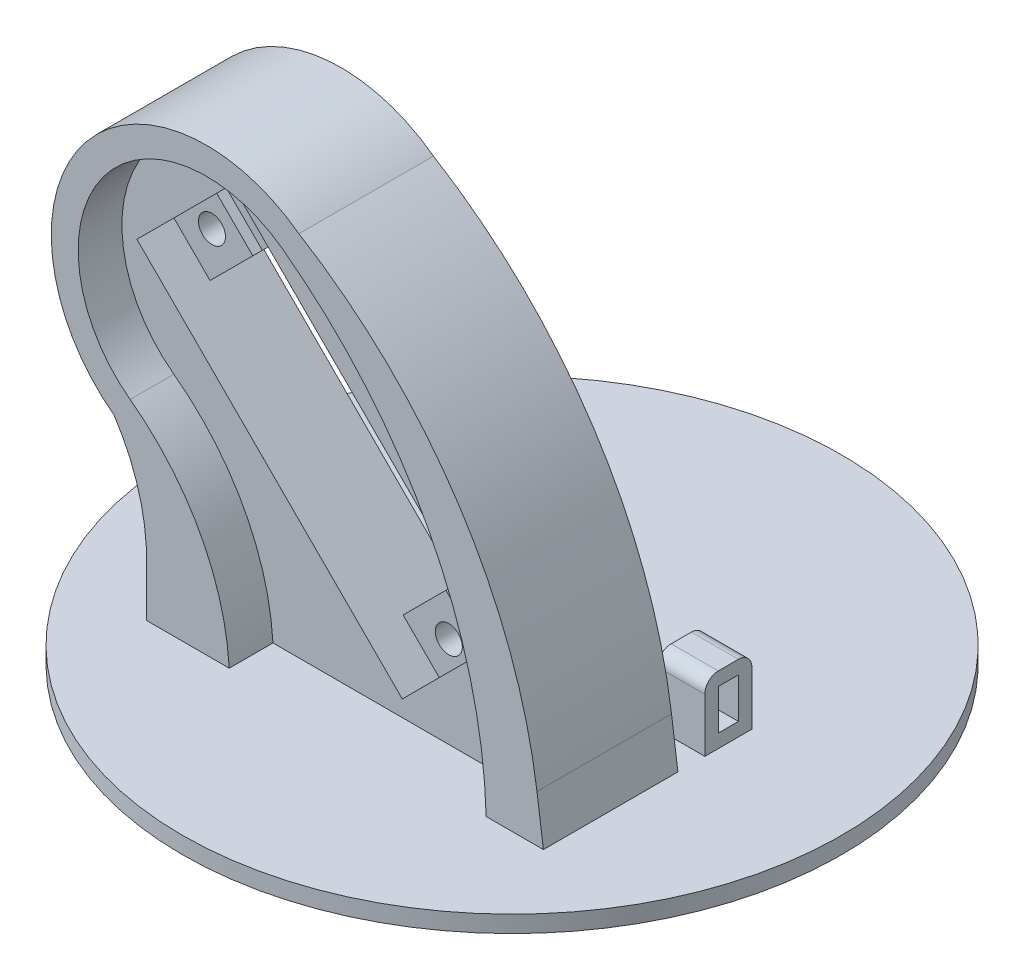
SolidWorks part; units mm, degrees
ref_plane "Front Plane" through (0, 0, 0) normal (0, 0, 1) x (1, 0, 0)
ref_plane "Top Plane" through (0, 0, 0) normal (0, 1, 0) x (1, 0, 0)
ref_plane "Right Plane" through (0, 0, 0) normal (1, 0, 0) x (0, 0, -1)
sketch "Sketch1" plane through (0, 0, 0) normal (0, 1, 0) x (1, 0, 0)
  circle A0 centre (0, 0) radius 49
  dimension "D1" = 98
extrude "Boss-Extrude1" add sketch "Sketch1" along normal blind 4
ref_plane "Plane1" through (0, 0, 4) normal (0, 0, 1) x (1, 0, 0)
sketch "Sketch3" plane through (0, 0, 4) normal (0, 0, 1) x (1, 0, 0)
  line L0 (-30.3479, 4) -> (28.6566, 4)
  line L2 (0, 11) -> (-28.4964, 39.4964)
  line L3 (14.1421, 25.1421) -> (-14.3543, 53.6385)
  line L4 (0, 11) -> (14.1421, 25.1421)
  line L5 (-28.4964, 39.4964) -> (-14.3543, 53.6385)
  line L6 (-30.3479, 4) -> (-30.3479, 11)
  line L9 (-14.2977, 39.4398) -> (-7.2266, 46.5109) construction
  line L10 (27.7023, 11) -> (28.6566, 4)
  circle A0 centre (-14.2977, 39.4398) radius 6
  arc A1 (-21.4253, 46.5675) -> (1.0561, 4) centre (-54.544, 1.8559) cw construction
  arc A2 (20.1509, 4) -> (-10.0661, 61.9029) centre (-54.544, 1.8559) ccw
  arc A3 (-18.0498, 4) -> (-32.7846, 31.232) centre (-54.544, 1.8559) ccw
  arc A5 (-10.0661, 61.9029) -> (-32.7846, 31.232) centre (-21.4253, 46.5675) ccw
  arc A7 (-7.6852, 65.1172) -> (-35.1655, 28.0178) centre (-21.4253, 46.5675) ccw
  arc A12 (5.5029, -42.622) -> (-10.0661, 61.9029) centre (-54.544, 1.8559) ccw construction
  arc A13 (-25.1679, -19.9035) -> (-32.7846, 31.232) centre (-54.544, 1.8559) ccw construction
  arc A14 (-28.3822, -17.5227) -> (8.7172, -45.0029) centre (-9.8325, -31.2628) ccw construction
  arc A15 (-28.3822, -17.5227) -> (-35.1655, 28.0178) centre (-54.544, 1.8559) ccw construction
  arc A16 (-25.1679, -19.9035) -> (5.5029, -42.622) centre (-9.8325, -31.2628) ccw construction
  arc A17 (8.7172, -45.0029) -> (-7.6852, 65.1172) centre (-54.544, 1.8559) ccw construction
  arc A18 (-30.3479, 11) -> (-35.1655, 28.0178) centre (-59.8626, 11.8355) ccw
  arc A19 (-7.6852, 65.1172) -> (27.7023, 11) centre (-46.9322, 0.8247) cw
  point P16 (0.4903, 10.0533)
  dimension "D6" = 12
  dimension "D1" = 4
  dimension "D3" = 40.3
  dimension "D5" = 10.08
  dimension "D4" = 20
extrude "Boss-Extrude2" add sketch "Sketch3" along normal blind 20 contours A19 A7 A18 L6 L0 A3 A5 A2 L10 region at (-29.3649, 7.5, 4)
extrude "Boss-Extrude3" add sketch "Sketch3<3>" along normal blind 13.5 contours A2 A5 A3 L0 L2 L5 L3 L4 region at (-21.631, 19.6646, 4)
sketch "Sketch3<3>" plane through (0, 0, 4) normal (0, 0, 1) x (1, 0, 0) same geometry as "Sketch3"
extrude "Boss-Extrude4" add sketch "Sketch3<4>" along normal up to surface (13.5 mm away) contours A0 | L5 L2 L4 L3 A0 region at (-6.0149, 31.157, 4) region at (-14.2977, 39.4398, 4) up to face at (-7.1771, 32.3193, 17.5)
sketch "Sketch3<4>" plane through (0, 0, 4) normal (0, 0, 1) x (1, 0, 0) same geometry as "Sketch3"
sketch "Sketch5" plane through (0, 0, 17.5) normal (0, 0, 1) x (1, 0, 0)
  line L0 (15.3215, 20.5473) -> (-24.1351, 60.0039)
  line L1 (1.1794, 6.4052) -> (-38.2772, 45.8618)
  line L2 (-38.2772, 45.8618) -> (-24.1351, 60.0039)
  line L3 (1.1794, 6.4052) -> (15.3215, 20.5473)
extrude "Cut-Extrude5" cut sketch "Sketch5" against normal blind 5.5
sketch "Sketch8" plane through (0, 0, 12) normal (0, 0, 1) x (1, 0, 0)
  line L0 (-32.9032, 40.4878) -> (-18.761, 54.6299)
  line L1 (-38.2772, 45.8618) -> (1.1794, 6.4052) construction
  line L2 (15.3215, 20.5473) -> (-24.1351, 60.0039) construction
  line L3 (-4.1946, 11.7792) -> (9.9475, 25.9214)
  line L4 (-24.1351, 60.0039) -> (-38.2772, 45.8618) construction
  line L11 (1.1794, 6.4052) -> (15.3215, 20.5473)
  line L12 (15.3215, 20.5473) -> (-24.1351, 60.0039)
  line L13 (-24.1351, 60.0039) -> (-38.2772, 45.8618)
  line L14 (-38.2772, 45.8618) -> (1.1794, 6.4052)
  line L15 (1.1794, 6.4052) -> (15.3215, 20.5473)
  line L16 (15.3215, 20.5473) -> (-24.1351, 60.0039)
  line L17 (-24.1351, 60.0039) -> (-38.2772, 45.8618)
  line L18 (-38.2772, 45.8618) -> (1.1794, 6.4052)
  line M8 (15.3215, 20.5473) -> (-24.1351, 60.0039)
  line M10 (-38.2772, 45.8618) -> (1.1794, 6.4052)
  dimension "D1" = 7.6
  dimension "D2" = 0
extrude "Cut-Extrude6" cut sketch "Sketch8" against normal blind 9 contours L3 L0 M10 M8 region at (-11.4778, 33.2046, 12)
sketch "Sketch11" plane through (0, 4, 0) normal (0, 1, 0) x (1, 0, 0)
  line L0 (28.6566, 0) -> (28.6566, 7)
  line L1 (28.6566, 7) -> (21.6566, 7)
  line L2 (21.6566, 7) -> (21.6566, 0)
  line L3 (21.6566, 0) -> (28.6566, 0)
  dimension "D1" = 7
  dimension "D2" = 7
extrude "Boss-Extrude5" add sketch "Sketch11" along normal blind 10
sketch "Sketch12" plane through (21.6566, 0, 0) normal (-1, 0, 0) x (0, 0, 1)
  line L8 (-5, 6) -> (-2, 6)
  line L9 (-2, 6) -> (-2, 12)
  line L10 (-2, 12) -> (-5, 12)
  line L11 (-5, 12) -> (-5, 6)
  line L12 (-5, 6) -> (-2, 6)
  line L13 (-2, 6) -> (-2, 12)
  line L14 (-2, 12) -> (-5, 12)
  line L15 (-5, 12) -> (-5, 6)
  dimension "D1" = 2
extrude "Cut-Extrude9" cut sketch "Sketch12" against normal up to next
fillet "Fillet1" radius 2 2 edges at (25.1566, 14, 0) (25.1566, 14, -7)
sketch "Sketch13" plane through (0, 4, 0) normal (0, 1, 0) x (1, 0, 0)
  circle A0 centre (0, 0) radius 1.27
  dimension "D1" = 2.54
extrude "Cut-Extrude10" cut sketch "Sketch13" against normal up to next
sketch "Sketch14" plane through (0, 0, 17.5) normal (0, 0, 1) x (1, 0, 0)
  line L0 (-49, 1.5) -> (50.2317, 1.5)
  line L1 (-49, 4) -> (-49, 0) construction
  line L2 (50.2317, 1.5) -> (50.2317, 0)
  line L3 (50.2317, 0) -> (-50.3039, 0)
  line L4 (-50.3039, 0) -> (-50.3039, 1.5)
  line L5 (-50.3039, 1.5) -> (-49, 1.5)
  dimension "D1" = 1.5
extrude "Cut-Extrude11" cut sketch "Sketch14" against normal mid plane 190
sketch "Sketch16" plane through (0, 0, 12) normal (0, 0, 1) x (1, 0, 0)
  line L0 (-31.2061, 52.9328) -> (8.2504, 13.4763) construction
  line L1 (-24.1351, 60.0039) -> (-38.2772, 45.8618) construction
  line L2 (1.1794, 6.4052) -> (15.3215, 20.5473) construction
  line L4 (-31.9132, 52.2257) -> (-26.5392, 46.8517)
  line L5 (-30.499, 53.6399) -> (-25.125, 48.2659)
  line L6 (8.9575, 14.1834) -> (3.5835, 19.5574)
  line L8 (-4.1946, 11.7792) -> (9.9475, 25.9214) construction
  line L9 (7.5433, 12.7692) -> (2.1693, 18.1432)
  line L10 (-38.2772, 45.8618) -> (-32.9032, 40.4878)
  line L11 (-32.9032, 40.4878) -> (-18.761, 54.6299)
  line L12 (-18.761, 54.6299) -> (-24.1351, 60.0039)
  line L13 (-24.1351, 60.0039) -> (-38.2772, 45.8618)
  line L14 (-38.2772, 45.8618) -> (-32.9032, 40.4878)
  line L15 (-32.9032, 40.4878) -> (-18.761, 54.6299)
  line L16 (-18.761, 54.6299) -> (-24.1351, 60.0039)
  line L17 (-24.1351, 60.0039) -> (-38.2772, 45.8618)
  line L22 (9.9475, 25.9214) -> (-4.1946, 11.7792)
  line L23 (-4.1946, 11.7792) -> (1.1794, 6.4052)
  line L24 (1.1794, 6.4052) -> (15.3215, 20.5473)
  line L25 (15.3215, 20.5473) -> (9.9475, 25.9214)
  line L26 (9.9475, 25.9214) -> (-4.1946, 11.7792)
  line L27 (-4.1946, 11.7792) -> (1.1794, 6.4052)
  line L28 (1.1794, 6.4052) -> (15.3215, 20.5473)
  line L29 (15.3215, 20.5473) -> (9.9475, 25.9214)
  line M12 (9.9475, 25.9214) -> (-4.1946, 11.7792)
  line M14 (1.1794, 6.4052) -> (15.3215, 20.5473)
  dimension "D1" = 0
  dimension "D2" = 2
  dimension "D3" = 1
  dimension "D4" = 0
extrude "Cut-Extrude12" cut sketch "Sketch16" against normal blind 2 contours L0 L28 L6 M12 | L0 L26 L9 M14 region at (5.917, 16.5168, 12) region at (5.2099, 15.8097, 12)
extrude "Cut-Extrude13" cut sketch "Sketch16<3>" against normal blind 2 contours L0 L17 L4 L15 | L17 L0 L15 L5 region at (-28.1656, 50.5994, 12) region at (-28.8727, 49.8923, 12)
sketch "Sketch16<3>" plane through (0, 0, 12) normal (0, 0, 1) x (1, 0, 0) same geometry as "Sketch16"
sketch "Sketch17" plane through (0, 4, 0) normal (0, 1, 0) x (1, 0, 0)
  circle A0 centre (8.18, 0) radius 1.09
  circle A1 centre (-8.18, 0) radius 1.09
  circle A2 centre (0, 8.18) radius 1.09
  point P9 (-12.0959, 17.1331)
  dimension "D1" = 2.18
  dimension "D5" = 2.18
  dimension "D6" = 2.18
  dimension "D2" = 8.18
  dimension "D3" = 8.18
  dimension "D4" = 8.18
extrude "Cut-Extrude14" cut sketch "Sketch17" against normal up to next
sketch "Sketch18" plane through (0, 0, 12) normal (0, 0, 1) x (1, 0, 0)
  line L0 (-4.1946, 11.7792) -> (2.1693, 18.1432) construction
  line L1 (-4.1946, 11.7792) -> (1.1794, 6.4052) construction
  line L2 (15.3215, 20.5473) -> (9.9475, 25.9214) construction
  line L3 (3.5835, 19.5574) -> (9.9475, 25.9214) construction
  line L4 (-38.2772, 45.8618) -> (-32.9032, 40.4878) construction
  line L5 (-32.9032, 40.4878) -> (-26.5392, 46.8517) construction
  line L6 (-25.125, 48.2659) -> (-18.761, 54.6299) construction
  line L11 (15.3215, 20.5473) -> (-24.1351, 60.0039) construction
  circle A0 centre (2.5936, 12.0621) radius 2.01
  circle A2 centre (9.6646, 19.1331) radius 2.01
  circle A3 centre (-32.6203, 47.276) radius 2.01
  circle A4 centre (-25.5493, 54.347) radius 2.01
  point P24 (-21.199, 57.0678)
  dimension "D5" = 4.02
  dimension "D6" = 4.02
  dimension "D9" = 4.02
  dimension "D12" = 4.02
  dimension "D1" = 4.6
  dimension "D2" = 5
  dimension "D3" = 5
  dimension "D4" = 4.6
  dimension "D7" = 5
  dimension "D8" = 4.6
  dimension "D10" = 4.6
  dimension "D11" = 5
extrude "Cut-Extrude15" cut sketch "Sketch18" against normal up to next
